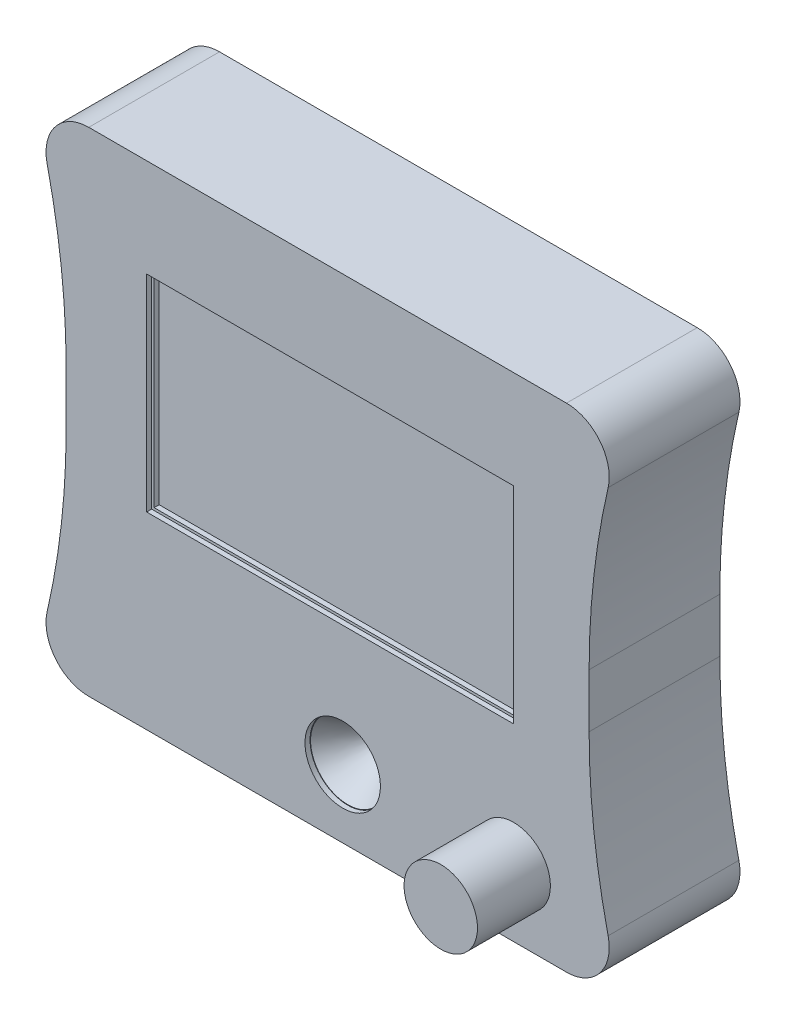
SolidWorks part; units mm, degrees
material "7075-T6 (SN)"
ref_plane "Plan de face" through (0, 0, 0) normal (0, 0, 1) x (1, 0, 0)
ref_plane "Plan de dessus" through (0, 0, 0) normal (0, 1, 0) x (1, 0, 0)
ref_plane "Plan de droite" through (0, 0, 0) normal (1, 0, 0) x (0, 0, -1)
sketch "Esquisse1" plane through (0, 0, 0) normal (0, 0, 1) x (1, 0, 0)
  line L1 (-39, 0) -> (39, 0)
  line L2 (-39, 0) -> (-39, 51)
  line L3 (-39, 51) -> (39, 51)
  line L4 (39, 0) -> (39, 51)
  dimension "D1" = 78
  dimension "D2" = 51
extrude "Boss.-Extru.1" add sketch "Esquisse1" along normal blind 8
sketch "Esquisse2" plane through (0, 0, 8) normal (0, 0, 1) x (1, 0, 0)
  line L0 (39, 51) -> (-39, 51) construction
  line L1 (-36, 45.5) -> (36, 45.5)
  line L2 (-36, 45.5) -> (-36, 5.5)
  line L3 (-36, 5.5) -> (36, 5.5)
  line L4 (36, 45.5) -> (36, 5.5)
  line L5 (36, 3.25) -> (-36, 3.25)
  line L6 (36, 3.25) -> (36, 2.25)
  line L7 (36, 2.25) -> (-36, 2.25)
  line L8 (-36, 3.25) -> (-36, 2.25)
  line L9 (-36, 47.75) -> (36, 47.75)
  line L10 (-36, 47.75) -> (-36, 48.75)
  line L11 (-36, 48.75) -> (36, 48.75)
  line L12 (36, 47.75) -> (36, 48.75)
  line L13 (0, 51) -> (0, 0) construction
  line L14 (-39, 25.5) -> (39, 25.5) construction
  line L15 (-39, 51) -> (-39, 0) construction
  line L16 (39, 0) -> (39, 51) construction
  dimension "D1" = 40
  dimension "D2" = 1
  dimension "D3" = 2.25
  dimension "D4" = 51
  dimension "D5" = 72
  dimension "D6" = 78
  dimension "D7" = 3
  dimension "D8" = 2.25
  dimension "D9" = 2.25
extrude "Enlèv. mat.-Extru.1" cut sketch "Esquisse2" against normal blind 1
sketch "Esquisse3" plane through (0, 0, 0) normal (0, 0, -1) x (-1, 0, 0)
  line L0 (39, 25.5) -> (44, 25.5) construction
  line L1 (39, 51) -> (39, 0) construction
  line L3 (39, 47) -> (44, 47)
  line L4 (39, 47) -> (39, 4)
  line L5 (39, 4) -> (44, 4)
  line L6 (44, 47) -> (44, 4)
  dimension "D1" = 43
  dimension "D2" = 5
extrude "Boss.-Extru.2" add sketch "Esquisse3" against normal blind 3.5 separate body
sketch "Esquisse4" plane through (0, 0, 0) normal (0, 0, -1) x (-1, 0, 0)
  line L0 (-46, 25) -> (0.5, 25) construction
  line L1 (-46, 60) -> (47, 60)
  line L2 (-46, 60) -> (-46, -10)
  line L3 (-46, -10) -> (47, -10)
  line L4 (47, 60) -> (47, -10)
  line L5 (0.5, 25) -> (0.5, -10) construction
  line L6 (-39, 51) -> (39, 51) construction
  line L7 (-39, 0) -> (-39, 51) construction
  circle A0 centre (-43.5, 57.5) radius 1.5
  circle A1 centre (-43.5, -7.5) radius 1.5
  circle A2 centre (44.5, 57.5) radius 1.5
  circle A3 centre (44.5, -7.5) radius 1.5
  dimension "D3" = 3
  dimension "D1" = 93
  dimension "D2" = 70
  dimension "D4" = 2.5
  dimension "D5" = 2.5
  dimension "D6" = 9
  dimension "D7" = 7
extrude "Boss.-Extru.3" add sketch "Esquisse4" along normal blind 1.5 separate body
ref_plane "Plan1" through (0, 0, -4) normal (0, 0, -1) x (-1, 0, 0)
sketch "Esquisse5" plane through (0, 0, -4) normal (0, 0, -1) x (-1, 0, 0)
  line L1 (-46, 60) -> (47, 60)
  line L2 (-46, 60) -> (-46, -27)
  line L3 (-46, -27) -> (47, -27)
  line L4 (47, 60) -> (47, -27)
  circle A0 centre (-43.5, 57.5) radius 1.5
  circle A1 centre (-43.5, -7.5) radius 1.5
  circle A2 centre (44.5, -7.5) radius 1.5
  circle A3 centre (44.5, 57.5) radius 1.5
  dimension "D1" = 87
extrude "Boss.-Extru.4" add sketch "Esquisse5" along normal blind 1.5 separate body
sketch "Esquisse6" plane through (-47, 0, 0) normal (-1, 0, 0) x (0, 0, 1)
  line L0 (-5.5, 38.5) -> (-8.5, 38.5)
  line L1 (-5.5, -27) -> (-5.5, 60) construction
  line L2 (-8.5, 38.5) -> (-8.5, 12)
  line L3 (-8.5, 12) -> (-5.5, 12)
  line L4 (-5.5, 60) -> (-4, 60) construction
  line L5 (-5.5, 38.25) -> (-8.25, 38.25)
  line L6 (-8.25, 38.25) -> (-8.25, 12.25)
  line L7 (-8.25, 12.25) -> (-5.5, 12.25)
  line L8 (-5.5, 38.5) -> (-5.5, 38.25)
  line L9 (-5.5, 12.25) -> (-5.5, 12)
  dimension "D1" = 21.5
  dimension "D2" = 26.5
  dimension "D3" = 3
  dimension "D4" = 0.25
extrude "Boss.-Extru.5" add sketch "Esquisse6" against normal blind 25 separate body
sketch "Esquisse7" plane through (0, 0, -5.5) normal (0, 0, -1) x (-1, 0, 0)
  line L0 (47, -27) -> (47, 60) construction
  line L1 (26, 53.5) -> (6, 53.5)
  line L2 (26, 53.5) -> (26, 44.5)
  line L3 (26, 44.5) -> (6, 44.5)
  line L4 (6, 53.5) -> (6, 44.5)
  line L5 (-24, 53.5) -> (-4, 53.5)
  line L6 (-24, 53.5) -> (-24, 44.5)
  line L7 (-24, 44.5) -> (-4, 44.5)
  line L8 (-4, 53.5) -> (-4, 44.5)
  line L9 (47, 60) -> (-46, 60) construction
  line L10 (-23, 52.5) -> (-5, 52.5)
  line L11 (-5, 52.5) -> (-5, 45.5)
  line L12 (-23, 45.5) -> (-5, 45.5)
  line L13 (-23, 52.5) -> (-23, 45.5)
  line L14 (25, 52.5) -> (7, 52.5)
  line L15 (7, 52.5) -> (7, 45.5)
  line L16 (25, 45.5) -> (7, 45.5)
  line L17 (25, 52.5) -> (25, 45.5)
  dimension "D1" = 20
  dimension "D2" = 9
  dimension "D3" = 10
  dimension "D4" = 21
  dimension "D5" = 6.5
  dimension "D6" = 1
extrude "Boss.-Extru.6" add sketch "Esquisse7" along normal blind 9 separate body
sketch "Esquisse8" plane through (0, 0, -4) normal (0, 0, 1) x (1, 0, 0)
  line L0 (46, -27) -> (-47, -27) construction
  line L1 (30.5, -13) -> (43.5, -13)
  line L2 (30.5, -13) -> (30.5, -24.5)
  line L3 (30.5, -24.5) -> (43.5, -24.5)
  line L4 (43.5, -13) -> (43.5, -24.5)
  line L5 (46, 60) -> (46, -27) construction
  line L6 (-47, -27) -> (-47, 60) construction
  line L7 (-42, -13) -> (-35, -13)
  line L8 (-42, -13) -> (-42, -19)
  line L9 (-42, -19) -> (-35, -19)
  line L10 (-35, -13) -> (-35, -19)
  dimension "D1" = 11.5
  dimension "D2" = 13
  dimension "D3" = 2.5
  dimension "D4" = 2.5
  dimension "D5" = 6
  dimension "D6" = 7
  dimension "D7" = 8
  dimension "D8" = 5
extrude "Boss.-Extru.7" add sketch "Esquisse8" along normal blind 4 separate body
sketch "Esquisse9" plane through (0, 0, 0) normal (0, 0, 1) x (1, 0, 0)
  line L0 (30.5, -24.5) -> (43.5, -24.5) construction
  line L1 (43.5, -13) -> (30.5, -13)
  line L2 (43.5, -13) -> (43.5, -24.5)
  line L3 (43.5, -24.5) -> (30.5, -24.5)
  line L4 (30.5, -13) -> (30.5, -24.5)
  line L5 (30.5, -13) -> (30.5, -24.5) construction
extrude "Boss.-Extru.8" add sketch "Esquisse9" along normal blind 3 separate body
sketch "Esquisse10" plane through (0, 0, 3) normal (0, 0, 1) x (1, 0, 0)
  circle A0 centre (37, -18.75) radius 3
  dimension "D1" = 6
extrude "Boss.-Extru.9" add sketch "Esquisse10" along normal blind 20 separate body
sketch "Esquisse11" plane through (0, 0, 23) normal (0, 0, 1) x (1, 0, 0)
  line L1 (38.7143, -16.288) -> (58.9108, -16.288)
  line L2 (38.7143, -16.288) -> (38.7143, -21.212)
  line L3 (38.7143, -21.212) -> (58.9108, -21.212)
  line L4 (58.9108, -16.288) -> (58.9108, -21.212)
  circle A0 centre (37, -18.75) radius 3 construction
extrude "Enlèv. mat.-Extru.2" cut sketch "Esquisse11" against normal blind 9
sketch "Esquisse12" plane through (0, 0, -4) normal (0, 0, 1) x (1, 0, 0)
  line L0 (46, -27) -> (-47, -27) construction
  line L1 (30.5, -13) -> (30.5, -24.5) construction
  circle A0 centre (18.5, -18) radius 6
  dimension "D1" = 12
  dimension "D2" = 9
  dimension "D3" = 12
extrude "Boss.-Extru.10" add sketch "Esquisse12" along normal blind 9.5 separate body
sketch "Esquisse13" plane through (0, 0, 0) normal (0, 0, 1) x (1, 0, 0)
  line L0 (-38, -13.5) -> (-39, -13.5)
  line L1 (-39, -13.5) -> (-39, -15.5)
  line L2 (-39, -15.5) -> (-41, -15.5)
  line L3 (-41, -15.5) -> (-41, -16.5)
  line L4 (-41, -16.5) -> (-39, -16.5)
  line L5 (-39, -16.5) -> (-39, -18.5)
  line L6 (-39, -18.5) -> (-38, -18.5)
  line L7 (-38, -18.5) -> (-38, -16.5)
  line L8 (-38, -16.5) -> (-36, -16.5)
  line L9 (-36, -16.5) -> (-36, -15.5)
  line L10 (-36, -15.5) -> (-38, -15.5)
  line L11 (-38, -15.5) -> (-38, -13.5)
  line L12 (-35, -19) -> (-42, -13) construction
  line L13 (-42, -13) -> (-42, -19) construction
  circle A0 centre (-38.5, -16) radius 3
  dimension "D1" = 1
  dimension "D2" = 2
  dimension "D3" = 0.5
  dimension "D4" = 0.5
extrude "Boss.-Extru.11" add sketch "Esquisse13" along normal blind 2 separate body
sketch "Esquisse14" plane through (0, 0, -4) normal (0, 0, 1) x (1, 0, 0)
  line L0 (46, -27) -> (-47, -27) construction
  line L1 (-0.5, -16) -> (5.5, -16)
  line L2 (-0.5, -16) -> (-0.5, -22)
  line L3 (-0.5, -22) -> (5.5, -22)
  line L4 (5.5, -16) -> (5.5, -22)
  line L5 (-47, -27) -> (-47, 60) construction
  dimension "D1" = 6
  dimension "D2" = 6
  dimension "D3" = 5
  dimension "D4" = 46.5
extrude "Boss.-Extru.12" add sketch "Esquisse14" along normal blind 3.3 separate body
sketch "Esquisse15" plane through (0, 0, -0.7) normal (0, 0, 1) x (1, 0, 0)
  line L0 (-0.5, -16) -> (5.5, -22) construction
  circle A0 centre (2.5, -19) radius 1.65
  dimension "D1" = 3.3
extrude "Boss.-Extru.13" add sketch "Esquisse15" along normal blind 1.5 separate body
sketch "Sketch1" plane through (0, 0, 0) normal (0, 0, 1) x (1, 0, 0)
  line L0 (-48, 61) -> (47, 61)
  line L1 (-47, 60) -> (46, 60) construction
  line L2 (47, 61) -> (47, -28) construction
  line L3 (-47, -27) -> (46, -27) construction
  line L5 (47, 50.0718) -> (47, -17.0718)
  line L6 (-48, -28) -> (47, -28)
  line L7 (-48, 50.0718) -> (-48, -17.0718)
  line L8 (-48, 61) -> (-48, -28) construction
  line L16 (-47, 60) -> (-47, -27) construction
  line L17 (46, 60) -> (46, -27) construction
  arc A4 (-48, 61) -> (-50, 53.5359) centre (-48, 57) ccw
  arc A5 (-48, -28) -> (-50, -20.5359) centre (-48, -24) cw
  arc A6 (47, -28) -> (49, -20.5359) centre (47, -24) ccw
  arc A7 (47, 61) -> (49, 53.5359) centre (47, 57) cw
  arc A9 (-50, -20.5359) -> (-48, -17.0718) centre (-52, -17.0718) ccw
  arc A10 (49, -20.5359) -> (47, -17.0718) centre (51, -17.0718) cw
  arc A11 (49, 53.5359) -> (47, 50.0718) centre (51, 50.0718) ccw
  arc A12 (-50, 53.5359) -> (-48, 50.0718) centre (-52, 50.0718) cw
  dimension "D2" = 4
  dimension "D1" = 1
extrude "Extrude-Thin1" add sketch "Sketch1" against normal up to vertex (5.5 mm away) and the other way up to vertex (8 mm away) separate body thin up to point (46, 60, -5.5) other way up to point (-39, 0, 8) thin type one direction wall 2
sketch "Sketch2" plane through (0, 0, -5.5) normal (0, 0, -1) x (-1, 0, 0)
  line L0 (0.5, 60) -> (0.5, 1.5007) construction
  line L1 (47, 60) -> (-46, 60) construction
  line L2 (44.5, 63) -> (44.5, 58.9) construction
  line L3 (44.45, 60.6) -> (44.45, 60.4047)
  line L4 (44.55, 60.6) -> (44.55, 60.4047)
  line L5 (42.05, 63) -> (-41.05, 63)
  line L6 (48, 63) -> (-47, 63)
  line L7 (-49, 50.0718) -> (-49, -17.0718)
  line L8 (-47, -30) -> (48, -30)
  line L9 (50, -17.0718) -> (50, 50.0718)
  line L10 (48, 63) -> (46.95, 63)
  line L11 (-49, 50.0718) -> (-49, -5.05)
  line L12 (-47, -30) -> (48, -30)
  line L13 (50, -17.0718) -> (50, -9.95)
  line L14 (44.45, 63) -> (44.45, 58.9) construction
  line L15 (44.55, 63) -> (44.55, 58.9) construction
  line L16 (45.9, -7.5) -> (50, -7.5) construction
  line L17 (47.4047, -7.55) -> (47.6, -7.55)
  line L18 (47.4047, -7.45) -> (47.6, -7.45)
  line L19 (45.9, -7.45) -> (50, -7.45) construction
  line L20 (45.9, -7.55) -> (50, -7.55) construction
  line L21 (50, -5.05) -> (50, 50.0718)
  line L22 (-44.9, -7.5) -> (-49, -7.5) construction
  line L23 (-46.4047, -7.45) -> (-46.6, -7.45)
  line L24 (-46.4047, -7.55) -> (-46.6, -7.55)
  line L25 (-43.5, 63) -> (-43.5, 58.9) construction
  line L26 (-43.55, 60.6) -> (-43.55, 60.4047)
  line L27 (-43.45, 60.6) -> (-43.45, 60.4047)
  line L28 (-45.95, 63) -> (-47, 63)
  line L29 (-49, -9.95) -> (-49, -17.0718)
  arc A0 (43.5974, 58.5702) -> (44.45, 60.4047) centre (42.05, 60.4047) ccw
  arc A1 (45.4026, 58.5702) -> (44.55, 60.4047) centre (46.95, 60.4047) cw
  arc A2 (43.5974, 58.5702) -> (45.4026, 58.5702) centre (44.5, 57.5) ccw
  arc A3 (46.95, 63) -> (44.55, 60.6) centre (46.95, 60.6) ccw
  arc A4 (44.45, 60.6) -> (42.05, 63) centre (42.05, 60.6) ccw
  arc A5 (47.4047, -7.55) -> (45.5702, -8.4026) centre (47.4047, -9.95) ccw
  arc A6 (47.4047, -7.45) -> (45.5702, -6.5974) centre (47.4047, -5.05) cw
  arc A7 (47.6, -7.55) -> (50, -9.95) centre (47.6, -9.95) cw
  arc A8 (45.5702, -6.5974) -> (45.5702, -8.4026) centre (44.5, -7.5) ccw
  arc A9 (47.6, -7.45) -> (50, -5.05) centre (47.6, -5.05) ccw
  arc A10 (51, 51.8038) -> (48, 63) centre (48, 57) ccw
  arc A11 (-47, 63) -> (-50, 51.8038) centre (-47, 57) ccw
  arc A12 (-49, 50.0718) -> (-50, 51.8038) centre (-51, 50.0718) ccw
  arc A13 (-50, -18.8038) -> (-49, -17.0718) centre (-51, -17.0718) ccw
  arc A14 (-50, -18.8038) -> (-47, -30) centre (-47, -24) ccw
  arc A15 (48, -30) -> (51, -18.8038) centre (48, -24) ccw
  arc A16 (50, -17.0718) -> (51, -18.8038) centre (52, -17.0718) ccw
  arc A17 (51, 51.8038) -> (50, 50.0718) centre (52, 50.0718) ccw
  arc A18 (51, 51.8038) -> (48, 63) centre (48, 57) ccw
  arc A19 (-47, 63) -> (-50, 51.8038) centre (-47, 57) ccw
  arc A20 (-49, 50.0718) -> (-50, 51.8038) centre (-51, 50.0718) ccw
  arc A21 (-50, -18.8038) -> (-49, -17.0718) centre (-51, -17.0718) ccw
  arc A22 (-50, -18.8038) -> (-47, -30) centre (-47, -24) ccw
  arc A23 (48, -30) -> (51, -18.8038) centre (48, -24) ccw
  arc A24 (50, -17.0718) -> (51, -18.8038) centre (52, -17.0718) ccw
  arc A25 (51, 51.8038) -> (50, 50.0718) centre (52, 50.0718) ccw
  arc A26 (-46.6, -7.45) -> (-49, -5.05) centre (-46.6, -5.05) cw
  arc A27 (-44.5702, -6.5974) -> (-44.5702, -8.4026) centre (-43.5, -7.5) cw
  arc A28 (-46.6, -7.55) -> (-49, -9.95) centre (-46.6, -9.95) ccw
  arc A29 (-46.4047, -7.45) -> (-44.5702, -6.5974) centre (-46.4047, -5.05) ccw
  arc A30 (-46.4047, -7.55) -> (-44.5702, -8.4026) centre (-46.4047, -9.95) cw
  arc A31 (-43.45, 60.6) -> (-41.05, 63) centre (-41.05, 60.6) cw
  arc A32 (-45.95, 63) -> (-43.55, 60.6) centre (-45.95, 60.6) cw
  arc A33 (-42.5974, 58.5702) -> (-44.4026, 58.5702) centre (-43.5, 57.5) cw
  arc A34 (-44.4026, 58.5702) -> (-43.55, 60.4047) centre (-45.95, 60.4047) ccw
  arc A35 (-42.5974, 58.5702) -> (-43.45, 60.4047) centre (-41.05, 60.4047) cw
  dimension "D3" = 0.05
  dimension "D4" = 2.4
  dimension "D5" = 0.05
  dimension "D2" = 0.05
  dimension "D7" = 2.4
  dimension "D8" = 2.4
  dimension "D1" = 0
  dimension "D6" = 0.05
extrude "Extrude-Thin2" add sketch "Sketch2" along normal blind 10 thin thin type one direction reverse wall 2
sketch "Sketch3" plane through (0, 0, -15.5) normal (0, 0, -1) x (-1, 0, 0)
  line L0 (-49, 50.0718) -> (-49, -17.0718)
  line L1 (-47, -30) -> (48, -30)
  line L2 (50, -17.0718) -> (50, 50.0718)
  line L3 (48, 63) -> (-47, 63)
  line L4 (-47, 50.0718) -> (-47, -17.0718)
  line L5 (-47, -28) -> (48, -28)
  line L6 (48, -17.0718) -> (48, 50.0718)
  line L7 (48, 61) -> (-47, 61)
  line L8 (-47, 50.0718) -> (-47, -17.0718) construction
  line L9 (-47, -28) -> (48, -28) construction
  line L10 (48, -17.0718) -> (48, 50.0718) construction
  line L11 (48, 61) -> (-47, 61) construction
  line L12 (26, 44.5) -> (26, 53.5) construction
  line L13 (26, 53.5) -> (6, 53.5) construction
  line L14 (6, 53.5) -> (6, 44.5) construction
  line L15 (6, 44.5) -> (26, 44.5) construction
  line L16 (-24, 53.5) -> (-24, 44.5) construction
  line L17 (-24, 44.5) -> (-4, 44.5) construction
  line L18 (-4, 44.5) -> (-4, 53.5) construction
  line L19 (-4, 53.5) -> (-24, 53.5) construction
  line L20 (26, 44.5) -> (26, 53.5) construction
  line L21 (26, 53.5) -> (6, 53.5) construction
  line L22 (6, 53.5) -> (6, 44.5) construction
  line L23 (6, 44.5) -> (26, 44.5) construction
  line L24 (-24, 53.5) -> (-24, 44.5) construction
  line L25 (-24, 44.5) -> (-4, 44.5) construction
  line L26 (-4, 44.5) -> (-4, 53.5) construction
  line L27 (-4, 53.5) -> (-24, 53.5) construction
  line L28 (26.5, 44) -> (26.5, 54)
  line L29 (26.5, 54) -> (5.5, 54)
  line L30 (5.5, 54) -> (5.5, 44)
  line L31 (5.5, 44) -> (26.5, 44)
  line L32 (-24.5, 54) -> (-24.5, 44)
  line L33 (-24.5, 44) -> (-3.5, 44)
  line L34 (-3.5, 44) -> (-3.5, 54)
  line L35 (-3.5, 54) -> (-24.5, 54)
  arc A0 (-50, -18.8038) -> (-49, -17.0718) centre (-51, -17.0718) ccw
  arc A1 (-50, -18.8038) -> (-47, -30) centre (-47, -24) ccw
  arc A2 (48, -30) -> (51, -18.8038) centre (48, -24) ccw
  arc A3 (50, -17.0718) -> (51, -18.8038) centre (52, -17.0718) ccw
  arc A4 (51, 51.8038) -> (50, 50.0718) centre (52, 50.0718) ccw
  arc A5 (51, 51.8038) -> (48, 63) centre (48, 57) ccw
  arc A6 (-47, 63) -> (-50, 51.8038) centre (-47, 57) ccw
  arc A7 (-49, 50.0718) -> (-50, 51.8038) centre (-51, 50.0718) ccw
  arc A8 (-49, -20.5359) -> (-47, -17.0718) centre (-51, -17.0718) ccw
  arc A9 (-49, -20.5359) -> (-47, -28) centre (-47, -24) ccw
  arc A10 (48, -28) -> (50, -20.5359) centre (48, -24) ccw
  arc A11 (48, -17.0718) -> (50, -20.5359) centre (52, -17.0718) ccw
  arc A12 (50, 53.5359) -> (48, 50.0718) centre (52, 50.0718) ccw
  arc A13 (50, 53.5359) -> (48, 61) centre (48, 57) ccw
  arc A14 (-47, 61) -> (-49, 53.5359) centre (-47, 57) ccw
  arc A15 (-47, 50.0718) -> (-49, 53.5359) centre (-51, 50.0718) ccw
  arc A16 (-49, -20.5359) -> (-47, -17.0718) centre (-51, -17.0718) ccw construction
  arc A17 (-49, -20.5359) -> (-47, -28) centre (-47, -24) ccw construction
  arc A18 (48, -28) -> (50, -20.5359) centre (48, -24) ccw construction
  arc A19 (48, -17.0718) -> (50, -20.5359) centre (52, -17.0718) ccw construction
  arc A20 (50, 53.5359) -> (48, 50.0718) centre (52, 50.0718) ccw construction
  arc A21 (50, 53.5359) -> (48, 61) centre (48, 57) ccw construction
  arc A22 (-47, 61) -> (-49, 53.5359) centre (-47, 57) ccw construction
  arc A23 (-47, 50.0718) -> (-49, 53.5359) centre (-51, 50.0718) ccw construction
  dimension "D1" = 0
  dimension "D2" = 2
  dimension "D3" = 0.5
extrude "Boss-Extrude1" add sketch "Sketch3" along normal blind 1
sketch "Sketch4" plane through (0, 0, 8) normal (0, 0, 1) x (1, 0, 0)
  line L0 (-50.5, 21.8432) -> (-50.5, 11.1568)
  line L1 (-48, -30.5) -> (47, -30.5)
  line L2 (49.5, 11.1568) -> (49.5, 21.8432)
  line L3 (47, 63.5) -> (-48, 63.5)
  line L4 (-50, 50.0718) -> (-50, -17.0718)
  line L5 (-48, -30) -> (47, -30)
  line L6 (49, -17.0718) -> (49, 50.0718)
  line L7 (47, 63) -> (-48, 63)
  line L8 (-50, 50.0718) -> (-50, -17.0718) construction
  line L9 (-48, -30) -> (47, -30) construction
  line L10 (49, -17.0718) -> (49, 50.0718) construction
  line L11 (47, 63) -> (-48, 63) construction
  line L12 (49.5, -17.0718) -> (49.5, 50.0718) construction
  line L13 (-50.5, 50.0718) -> (-50.5, -17.0718) construction
  arc A0 (50.25, 51.3708) -> (47, 63.5) centre (47, 57) ccw construction
  arc A1 (-54.3339, -22.5398) -> (-48, -30.5) centre (-48, -24) ccw
  arc A2 (47, -30.5) -> (53.3339, -22.5398) centre (47, -24) ccw
  arc A3 (-48, 63.5) -> (-51.25, 51.3708) centre (-48, 57) ccw construction
  arc A4 (-51.25, -18.3708) -> (-48, -30.5) centre (-48, -24) ccw construction
  arc A5 (53.3339, 55.5398) -> (47, 63.5) centre (47, 57) ccw
  arc A6 (-48, 63.5) -> (-54.3339, 55.5398) centre (-48, 57) ccw
  arc A7 (47, -30.5) -> (50.25, -18.3708) centre (47, -24) ccw construction
  arc A8 (-48, 63) -> (-51, 51.8038) centre (-48, 57) ccw
  arc A9 (-50, 50.0718) -> (-51, 51.8038) centre (-52, 50.0718) ccw
  arc A10 (-51, -18.8038) -> (-50, -17.0718) centre (-52, -17.0718) ccw
  arc A11 (-51, -18.8038) -> (-48, -30) centre (-48, -24) ccw
  arc A12 (47, -30) -> (50, -18.8038) centre (47, -24) ccw
  arc A13 (49, -17.0718) -> (50, -18.8038) centre (51, -17.0718) ccw
  arc A14 (50, 51.8038) -> (49, 50.0718) centre (51, 50.0718) ccw
  arc A15 (50, 51.8038) -> (47, 63) centre (47, 57) ccw
  arc A16 (-48, 63) -> (-51, 51.8038) centre (-48, 57) ccw construction
  arc A17 (-50, 50.0718) -> (-51, 51.8038) centre (-52, 50.0718) ccw construction
  arc A18 (-51, -18.8038) -> (-50, -17.0718) centre (-52, -17.0718) ccw construction
  arc A19 (-51, -18.8038) -> (-48, -30) centre (-48, -24) ccw construction
  arc A20 (47, -30) -> (50, -18.8038) centre (47, -24) ccw construction
  arc A21 (49, -17.0718) -> (50, -18.8038) centre (51, -17.0718) ccw construction
  arc A22 (50, 51.8038) -> (49, 50.0718) centre (51, 50.0718) ccw construction
  arc A23 (50, 51.8038) -> (47, 63) centre (47, 57) ccw construction
  arc A24 (-50.5, 50.0718) -> (-51.25, 51.3708) centre (-52, 50.0718) ccw construction
  arc A25 (-51.25, -18.3708) -> (-50.5, -17.0718) centre (-52, -17.0718) ccw construction
  arc A26 (49.5, -17.0718) -> (50.25, -18.3708) centre (51, -17.0718) ccw construction
  arc A27 (50.25, 51.3708) -> (49.5, 50.0718) centre (51, 50.0718) ccw construction
  arc A28 (-54.3339, -22.5398) -> (-50.5, 11.1568) centre (-200.5, 11.1568) ccw
  arc A29 (-50.5, 21.8432) -> (-54.3339, 55.5398) centre (-200.5, 21.8432) ccw
  arc A30 (49.5, 21.8432) -> (53.3339, 55.5398) centre (199.5, 21.8432) cw
  arc A31 (53.3339, -22.5398) -> (49.5, 11.1568) centre (199.5, 11.1568) cw
  dimension "D3" = 150
  dimension "D1" = 0
  dimension "D2" = 0.5
extrude "Extrude-Thin3" add sketch "Sketch4" against normal blind 25 separate body thin thin type one direction wall 2
sketch "Sketch5" plane through (0, 0, 8) normal (0, 0, 1) x (1, 0, 0)
  line L4 (-52.5, 21.8432) -> (-52.5, 11.1568)
  line L5 (-48, -32.5) -> (47, -32.5)
  line L6 (51.5, 11.1568) -> (51.5, 21.8432)
  line L7 (47, 65.5) -> (-48, 65.5)
  line L8 (-52.5, 21.8432) -> (-52.5, 11.1568)
  line L9 (-48, -32.5) -> (47, -32.5)
  line L10 (51.5, 11.1568) -> (51.5, 21.8432)
  line L11 (47, 65.5) -> (-48, 65.5)
  line L16 (-36.5, 46) -> (-36.5, 5)
  line L17 (-36.5, 5) -> (36.5, 5)
  line L18 (36.5, 5) -> (36.5, 46)
  line L19 (36.5, 46) -> (-36.5, 46)
  line L20 (-36.5, 46) -> (-36.5, 5)
  line L21 (-36.5, 5) -> (36.5, 5)
  line L22 (36.5, 5) -> (36.5, 46)
  line L23 (36.5, 46) -> (-36.5, 46)
  circle A0 centre (37, -18.75) radius 3.9
  circle A1 centre (2.5, -19) radius 7.5
  arc A4 (-48, 65.5) -> (-56.2827, 55.0905) centre (-48, 57) ccw
  arc A5 (-56.2827, -22.0905) -> (-48, -32.5) centre (-48, -24) ccw
  arc A6 (47, -32.5) -> (55.2827, -22.0905) centre (47, -24) ccw
  arc A7 (55.2827, 55.0905) -> (47, 65.5) centre (47, 57) ccw
  arc A8 (-48, 65.5) -> (-56.2827, 55.0905) centre (-48, 57) ccw
  arc A9 (-56.2827, -22.0905) -> (-48, -32.5) centre (-48, -24) ccw
  arc A10 (47, -32.5) -> (55.2827, -22.0905) centre (47, -24) ccw
  arc A11 (55.2827, 55.0905) -> (47, 65.5) centre (47, 57) ccw
  arc A18 (51.5, 11.1568) -> (55.2827, -22.0905) centre (199.5, 11.1568) ccw
  arc A19 (51.5, 11.1568) -> (55.2827, -22.0905) centre (199.5, 11.1568) ccw
  arc A20 (55.2827, 55.0905) -> (51.5, 21.8432) centre (199.5, 21.8432) ccw
  arc A21 (55.2827, 55.0905) -> (51.5, 21.8432) centre (199.5, 21.8432) ccw
  arc A22 (-52.5, 21.8432) -> (-56.2827, 55.0905) centre (-200.5, 21.8432) ccw
  arc A23 (-52.5, 21.8432) -> (-56.2827, 55.0905) centre (-200.5, 21.8432) ccw
  arc A24 (-56.2827, -22.0905) -> (-52.5, 11.1568) centre (-200.5, 11.1568) ccw
  arc A25 (-56.2827, -22.0905) -> (-52.5, 11.1568) centre (-200.5, 11.1568) ccw
  dimension "D1" = 0
  dimension "D2" = 0.5
extrude "Boss-Extrude2" add sketch "Sketch5" along normal blind 1
sketch "Sketch6" plane through (0, 0, 8) normal (0, 0, -1) x (-1, 0, 0)
  circle A1 centre (-2.5, -19) radius 7.5 construction
  circle A2 centre (-2.5, -19) radius 7.5
ref_plane "Plane1" through (2.5, 0, 0) normal (1, 0, 0) x (0, 0, -1)
sketch "Sketch7" plane through (2.5, 0, 0) normal (1, 0, 0) x (0, 0, -1)
  line L0 (-8, -19) -> (6.5, -19) construction
  line L1 (-8, -19) -> (-8, -11.6) construction
  line L2 (-8, -11.6) -> (-1.2689, -16.2792)
  line L3 (-8, -9.1642) -> (-1.2689, -13.8434)
  line L4 (-1.2689, -16.2792) -> (-1.2689, -13.8434)
  line L5 (-6.8584, -9.9578) -> (-0.1273, -14.637) construction
  line L6 (-8, -11.6) -> (-8, -9.1642)
  dimension "D1" = 2
revolve "Revolve1" add sketch "Sketch7" angle 360 about L0
sketch "Sketch8" plane through (0, 0, 9) normal (0, 0, 1) x (1, 0, 0)
  line L2 (39.0143, -16.288) -> (39.0143, -21.212)
  line L3 (39.0143, -16.2635) -> (39.0143, -21.2365)
  arc A0 (39.0143, -16.2635) -> (39.0143, -21.2365) centre (37, -18.75) ccw
  dimension "D1" = 0.3
extrude "Extrude-Thin4" add sketch "Sketch8" along normal blind 8 from offset 6 separate body thin thin type one direction wall 2
sketch "Sketch9" plane through (0, 0, 23) normal (0, 0, 1) x (1, 0, 0)
  circle A0 centre (37, -18.75) radius 5.3
extrude "Extrude-Thin5" add sketch "Sketch9" against normal blind 13.5 separate body thin thin type one direction wall 2
sketch "Sketch10" plane through (0, 0, 23) normal (0, 0, 1) x (1, 0, 0)
  circle A1 centre (37, -18.75) radius 7.3
  circle A2 centre (37, -18.75) radius 7.3
  dimension "D1" = 0
extrude "Boss-Extrude3" add sketch "Sketch10" along normal blind 1
equation "\"D7@Esquisse2\"=(\"D6@Esquisse2\"-\"D5@Esquisse2\")/2"
equation "\"D8@Esquisse2\"=\"D3@Esquisse2\""
equation "\"D9@Esquisse2\"=\"D3@Esquisse2\""
equation "\"D3@Esquisse2\"=(\"D4@Esquisse2\"-\"D1@Esquisse2\"-(2*\"D2@Esquisse2\"))/4"
